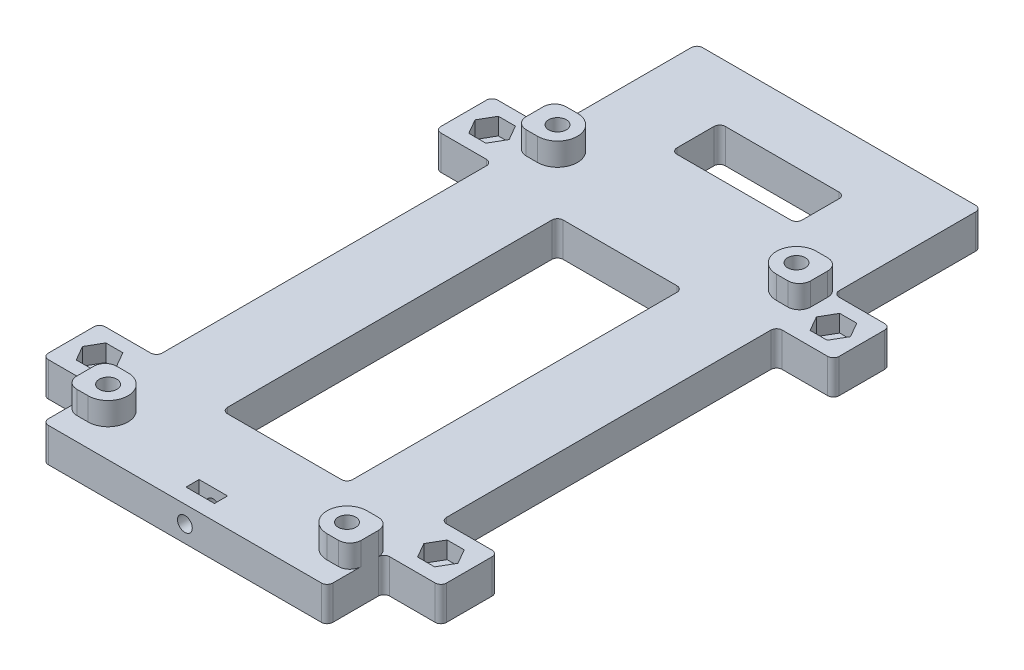
SolidWorks part; units mm, degrees
ref_plane "Front Plane" through (0, 0, 0) normal (0, 0, 1) x (1, 0, 0)
ref_plane "Top Plane" through (0, 0, 0) normal (0, 1, 0) x (1, 0, 0)
ref_plane "Right Plane" through (0, 0, 0) normal (1, 0, 0) x (0, 0, -1)
sketch "Sketch1" plane through (0, 0, 0) normal (0, 1, 0) x (1, 0, 0)
  line L1 (-25, 57.5) -> (25, 57.5)
  line L2 (-25, 57.5) -> (-25, -57.5)
  line L3 (-25, -57.5) -> (25, -57.5)
  line L4 (25, 57.5) -> (25, -57.5)
  line L5 (-25, 57.5) -> (25, -57.5) construction
  line L6 (-25, -57.5) -> (25, 57.5) construction
  line L7 (-21, 29) -> (21, 29) construction
  line L8 (-21, 29) -> (-21, -50) construction
  line L9 (-21, -50) -> (21, -50) construction
  line L10 (21, 29) -> (21, -50) construction
  line L11 (-21, 29) -> (21, -50) construction
  line L12 (-21, -50) -> (21, 29) construction
  circle A0 centre (-21, 29) radius 1.55
  circle A1 centre (21, 29) radius 1.55
  circle A2 centre (21, -50) radius 1.55
  circle A3 centre (-21, -50) radius 1.55
  point P0 (0, 0)
  point P6 (0, -10.5)
  dimension "D6" = 3.1
  dimension "D5" = 7.5
  dimension "D1" = 50
  dimension "D2" = 115
  dimension "D3" = 42
  dimension "D4" = 79
extrude "Boss-Extrude1" add sketch "Sketch1" along normal blind 6
sketch "Sketch2" plane through (0, 0, 0) normal (0, -1, 0) x (1, 0, 0)
  circle A0 centre (-21, 50) radius 3.25
  circle A1 centre (21, 50) radius 3.25
  circle A2 centre (21, -29) radius 3.25
  circle A3 centre (-21, -29) radius 3.25
  dimension "D1" = 6.5
extrude "Cut-Extrude1" cut sketch "Sketch2" against normal blind 4.5
sketch "Sketch3" plane through (0, 6, 0) normal (0, 1, 0) x (1, 0, 0)
  line L0 (-25, 57.5) -> (-25, -57.5) construction
  line L1 (-21, 32.5) -> (-25, 32.5)
  line L2 (-21, 32.5) -> (-21, 25.5)
  line L3 (-21, 25.5) -> (-25, 25.5)
  line L4 (-25, 32.5) -> (-25, 25.5)
  line L5 (25, -57.5) -> (25, 57.5) construction
  line L6 (21, 32.5) -> (25, 32.5)
  line L7 (21, 32.5) -> (21, 25.5)
  line L8 (21, 25.5) -> (25, 25.5)
  line L9 (25, 32.5) -> (25, 25.5)
  line L11 (21, -46.5) -> (25, -46.5)
  line L12 (21, -46.5) -> (21, -53.5)
  line L13 (21, -53.5) -> (25, -53.5)
  line L14 (25, -46.5) -> (25, -53.5)
  line L15 (-21, -46.5) -> (-25, -46.5)
  line L16 (-21, -46.5) -> (-21, -53.5)
  line L17 (-21, -53.5) -> (-25, -53.5)
  line L18 (-25, -46.5) -> (-25, -53.5)
  circle A0 centre (21, 29) radius 3.5
  circle A1 centre (-21, 29) radius 3.5
  circle A2 centre (-21, -50) radius 3.5
  circle A3 centre (21, -50) radius 3.5
  circle M1 centre (-21, 29) radius 1.55
  circle M2 centre (21, 29) radius 1.55
  line M3 (25, -57.5) -> (25, 57.5)
  line M5 (-25, 57.5) -> (-25, -57.5)
  circle M7 centre (21, -50) radius 1.55
  circle M8 centre (-21, -50) radius 1.55
  dimension "D1" = 7
extrude "Boss-Extrude2" add sketch "Sketch3" along normal blind 4 contours A1 L1 L3 M5 | L2 A1 M1 | L2 A1 M1 | L7 A0 M2 | L7 A0 M2 | A0 L8 L6 M3 | A3 L13 L11 M3 | L12 A3 M7 | L12 A3 M7 | L16 A2 M8 | L16 A2 M8 | A2 L15 L17 M5 region at (-24.5806, 6, -29) region at (-19.3126, 6, -29) region at (-23, 6, 46.5806) region at (-22.6874, 6, -29) region at (-19.3126, 6, 50) region at (-22.6874, 6, 50) region at (24.9194, 6, 50) region at (22.6874, 6, -29) region at (23, 6, -32.4194) region at (19.3126, 6, -29) region at (22.6874, 6, 50) region at (19.3126, 6, 50)
sketch "Sketch4" plane through (0, 0, 0) normal (0, -1, 0) x (1, 0, 0)
  line L0 (-25, -57.5) -> (-25, 57.5) construction
  line L1 (-25, 47.5) -> (-35, 47.5)
  line L2 (-25, 47.5) -> (-25, 37.5)
  line L3 (-25, 37.5) -> (-35, 37.5)
  line L4 (-35, 47.5) -> (-35, 37.5)
  line L5 (-25, -31.5) -> (-35, -31.5)
  line L6 (-25, -31.5) -> (-25, -21.5)
  line L7 (-25, -21.5) -> (-35, -21.5)
  line L8 (-35, -31.5) -> (-35, -21.5)
  line L9 (25, 57.5) -> (25, -57.5) construction
  line L10 (25, -21.5) -> (35, -21.5)
  line L11 (25, -21.5) -> (25, -31.5)
  line L12 (25, -31.5) -> (35, -31.5)
  line L13 (35, -21.5) -> (35, -31.5)
  line L15 (25, 47.5) -> (35, 47.5)
  line L16 (25, 47.5) -> (25, 37.5)
  line L17 (25, 37.5) -> (35, 37.5)
  line L18 (35, 47.5) -> (35, 37.5)
  line L19 (-25, -25.5) -> (-25, 46.5) construction
  line L20 (-25, 57.5) -> (25, 57.5) construction
  line L21 (25, 46.5) -> (25, -25.5) construction
  dimension "D1" = 10
  dimension "D2" = 10
  dimension "D3" = 10
  dimension "D4" = 10
  dimension "D5" = 59
extrude "Boss-Extrude3" add sketch "Sketch4" against normal blind 6
sketch "Sketch5" plane through (0, 6, 0) normal (0, 1, 0) x (1, 0, 0)
  line L1 (35, -47.5) -> (-35, -47.5) construction
  line L2 (35, -47.5) -> (35, 31.5) construction
  line L3 (35, 31.5) -> (-35, 31.5) construction
  line L4 (-35, -47.5) -> (-35, 31.5) construction
  line L5 (-30, 26.5) -> (30, 26.5) construction
  line L6 (-30, 26.5) -> (-30, -42.5) construction
  line L7 (-30, -42.5) -> (30, -42.5) construction
  line L8 (30, 26.5) -> (30, -42.5) construction
  circle A0 centre (-30, 26.5) radius 1.25
  circle A1 centre (30, 26.5) radius 1.25
  circle A2 centre (30, -42.5) radius 1.25
  circle A3 centre (-30, -42.5) radius 1.25
  dimension "D4" = 2.5
  dimension "D1" = 5
  dimension "D2" = 5
  dimension "D3" = 5
  dimension "D5" = 5
extrude "Cut-Extrude2" cut sketch "Sketch5" against normal blind 6
sketch "Sketch6" plane through (0, 6, 0) normal (0, 1, 0) x (1, 0, 0)
  line L0 (25, 57.5) -> (-25, 57.5) construction
  line L1 (-11, 19) -> (11, 19)
  line L2 (-11, 19) -> (-11, -40)
  line L3 (-11, -40) -> (11, -40)
  line L4 (11, 19) -> (11, -40)
  line L5 (-11, 19) -> (11, -40) construction
  line L6 (-11, -40) -> (11, 19) construction
  line L7 (-11, 47.5) -> (11, 47.5)
  line L8 (-11, 47.5) -> (-11, 39)
  line L9 (-11, 39) -> (11, 39)
  line L10 (11, 47.5) -> (11, 39)
  line L11 (-11, 47.5) -> (11, 39) construction
  line L12 (-11, 39) -> (11, 47.5) construction
  arc A0 (-21, 25.5) -> (-21, 32.5) centre (-21, 29) ccw construction
  arc A1 (-21, 25.5) -> (-21, 32.5) centre (-21, 29) ccw construction
  arc A2 (-21, -53.5) -> (-21, -46.5) centre (-21, -50) ccw construction
  arc A3 (-21, -53.5) -> (-21, -46.5) centre (-21, -50) ccw construction
  arc A4 (21, -46.5) -> (21, -53.5) centre (21, -50) ccw construction
  point P0 (0, -10.5)
  point P5 (0, 43.25)
  dimension "D2" = 10
  dimension "D5" = 10
  dimension "D1" = 10
  dimension "D3" = 10
  dimension "D4" = 10
  dimension "D6" = 10
extrude "Cut-Extrude3" cut sketch "Sketch6" against normal through all both and the other way through all
sketch "Sketch7" plane through (0, 0, 57.5) normal (0, 0, 1) x (1, 0, 0)
  line L0 (-25, 3) -> (25, 3) construction
  line L1 (-25, 6) -> (-25, 0) construction
  line L2 (25, 6) -> (25, 0) construction
  circle A0 centre (0, 3) radius 1.3
  dimension "D1" = 2.6
extrude "Cut-Extrude4" cut sketch "Sketch7" against normal blind 25
sketch "Sketch8" plane through (0, 6, 0) normal (0, 1, 0) x (1, 0, 0)
  line L0 (-25, -57.5) -> (25, -57.5) construction
  line L1 (-2.5, -52.5) -> (2.5, -52.5)
  line L2 (-2.5, -52.5) -> (-2.5, -54.8)
  line L3 (-2.5, -54.8) -> (2.5, -54.8)
  line L4 (2.5, -52.5) -> (2.5, -54.8)
  line L5 (-2.5, -52.5) -> (2.5, -54.8) construction
  line L6 (-2.5, -54.8) -> (2.5, -52.5) construction
  point P0 (0, -53.65)
  dimension "D1" = 5
  dimension "D2" = 2.3
  dimension "D3" = 5
extrude "Cut-Extrude5" cut sketch "Sketch8" against normal through all both and the other way through all
sketch "Sketch9" plane through (0, 6, 0) normal (0, 1, 0) x (1, 0, 0)
  line L1 (-27, 26.5) -> (-28.5, 29.0981)
  line L2 (-28.5, 29.0981) -> (-31.5, 29.0981)
  line L3 (-31.5, 29.0981) -> (-33, 26.5)
  line L4 (-33, 26.5) -> (-31.5, 23.9019)
  line L5 (-31.5, 23.9019) -> (-28.5, 23.9019)
  line L6 (-28.5, 23.9019) -> (-27, 26.5)
  line L7 (33, 26.5) -> (31.5, 29.0981)
  line L8 (31.5, 29.0981) -> (28.5, 29.0981)
  line L9 (28.5, 29.0981) -> (27, 26.5)
  line L10 (27, 26.5) -> (28.5, 23.9019)
  line L11 (28.5, 23.9019) -> (31.5, 23.9019)
  line L12 (31.5, 23.9019) -> (33, 26.5)
  line L13 (33, -42.5) -> (31.5, -39.9019)
  line L14 (31.5, -39.9019) -> (28.5, -39.9019)
  line L15 (28.5, -39.9019) -> (27, -42.5)
  line L16 (27, -42.5) -> (28.5, -45.0981)
  line L17 (28.5, -45.0981) -> (31.5, -45.0981)
  line L18 (31.5, -45.0981) -> (33, -42.5)
  line L19 (-27, -42.5) -> (-28.5, -39.9019)
  line L20 (-28.5, -39.9019) -> (-31.5, -39.9019)
  line L21 (-31.5, -39.9019) -> (-33, -42.5)
  line L22 (-33, -42.5) -> (-31.5, -45.0981)
  line L23 (-31.5, -45.0981) -> (-28.5, -45.0981)
  line L24 (-28.5, -45.0981) -> (-27, -42.5)
  circle A0 centre (-30, 26.5) radius 2.5981 construction
  circle A1 centre (30, 26.5) radius 2.5981 construction
  circle A2 centre (30, -42.5) radius 2.5981 construction
  circle A3 centre (-30, -42.5) radius 2.5981 construction
  dimension "D1" = 6
extrude "Cut-Extrude6" cut sketch "Sketch9" against normal blind 3
fillet "Fillet1" radius 1 28 edges at (11, 3, 40) (-11, 3, 40) (-11, 3, -19) (11, 3, -19) (11, 3, -47.5) (-11, 3, -47.5) (-11, 3, -39) (11, 3, -39) (-25, 3, -57.5) (25, 3, -31.5) (-25, 3, -31.5) (-35, 3, -31.5) (-25, 3, -21.5) (-35, 3, -21.5) (25, 3, -57.5) (35, 3, -31.5) (35, 3, -21.5) (25, 3, -21.5) (-25, 3, 37.5) (-35, 3, 37.5) (25, 3, 37.5) (35, 3, 37.5) (25, 3, 47.5) (-25, 3, 47.5) (-35, 3, 47.5) (-25, 3, 57.5) (25, 3, 57.5) (35, 3, 47.5)
fillet "Fillet2" radius 2 8 edges at (25, 8, -25.5) (25, 8, -32.5) (25, 8, 53.5) (25, 8, 46.5) (-25, 8, 53.5) (-25, 8, 46.5) (-25, 8, -25.5) (-25, 8, -32.5)
